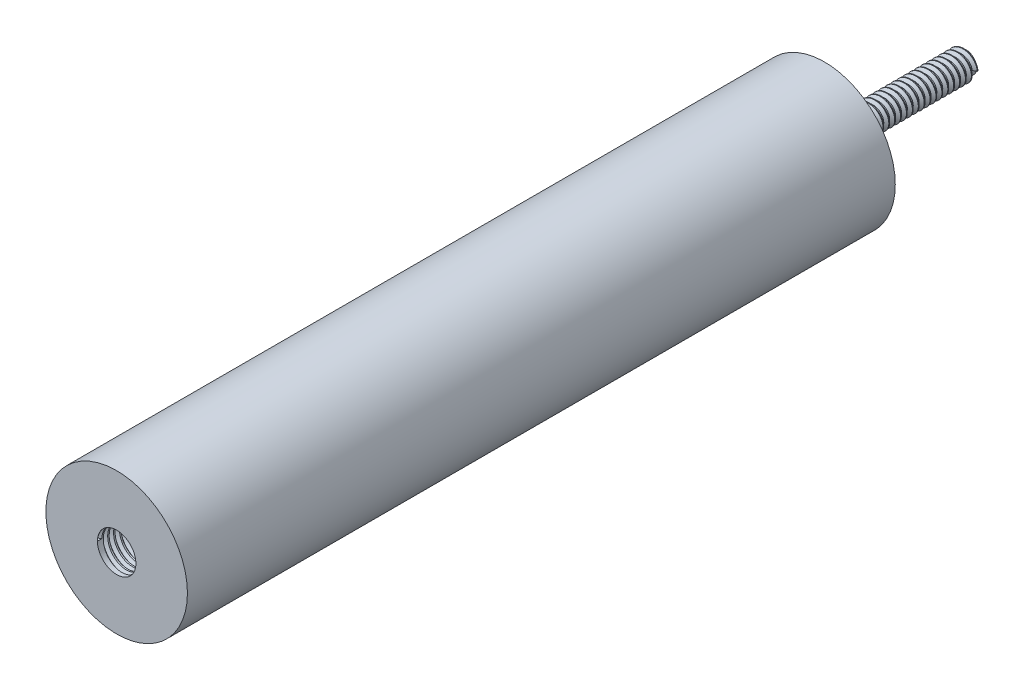
SolidWorks part; units mm, degrees
material "Cast Carbon Steel"
ref_plane "Front Plane" through (0, 0, 0) normal (0, 0, 1) x (1, 0, 0)
ref_plane "Top Plane" through (0, 0, 0) normal (0, 1, 0) x (1, 0, 0)
ref_plane "Right Plane" through (0, 0, 0) normal (1, 0, 0) x (0, 0, -1)
sketch "Sketch1" plane through (0, 0, 0) normal (0, 0, 1) x (1, 0, 0)
  line L1 (0, 0) -> (25.4, 0)
  line L2 (0, 0) -> (0, 32.766)
  line L3 (0, 32.766) -> (25.4, 32.766)
  line L4 (25.4, 0) -> (25.4, 32.766)
  dimension "D1" = 25.4
  dimension "D2" = 32.766
extrude "Boss-Extrude1" add sketch "Sketch1" against normal blind 127
sketch "Sketch2" plane through (0, 0, 0) normal (0, 0, 1) x (1, 0, 0)
  line L0 (25.4, 32.766) -> (0, 32.766) construction
  line L1 (25.4, 0) -> (25.4, 32.766) construction
  line L3 (0, 32.766) -> (25.4, 32.766)
  line L4 (0, 32.766) -> (0, 0)
  line L5 (0, 0) -> (25.4, 0)
  line L6 (25.4, 32.766) -> (25.4, 0)
  circle A0 centre (12.7, 16.383) radius 2.4574
  dimension "D1" = 4.9149
  dimension "D2" = 16.383
  dimension "D3" = 12.7
extrude "Cut-Extrude2" cut sketch "Sketch2" against normal blind 25.4
sketch "Sketch5" plane through (0, 0, -25.4) normal (0, 0, 1) x (1, 0, 0)
  line L0 (25.4, 32.766) -> (0, 32.766) construction
  line L1 (25.4, 0) -> (25.4, 32.766) construction
  line L3 (0, 32.766) -> (25.4, 32.766)
  line L4 (0, 32.766) -> (0, 0)
  line L5 (0, 0) -> (25.4, 0)
  line L6 (25.4, 32.766) -> (25.4, 0)
  circle A0 centre (12.7, 16.383) radius 12.7
  line M1 (0, 32.766) -> (0, 0)
  line M2 (0, 0) -> (25.4, 0)
  line M3 (25.4, 0) -> (25.4, 32.766)
  line M4 (25.4, 32.766) -> (0, 32.766)
  dimension "D1" = 16.383
  dimension "D3" = 25.4
  dimension "D2" = 12.7
extrude "Cut-Extrude3" cut sketch "Sketch5" against normal up to surface (101.6 mm away) contours A0 L6 M4 M1 | A0 L4 M2 M3 region at (12.7, 32.4637, -25.4) region at (12.7, 3.3807, -25.4) up to face at (12.7, 16.383, -127)
sketch "Sketch7" plane through (0, 0, -127) normal (0, 0, -1) x (-1, 0, 0)
  circle A0 centre (-12.7, 16.383) radius 1.8986
  dimension "D1" = 3.7973
extrude "Boss-Extrude2" add sketch "Sketch7" along normal blind 25.4
thread "Thread3" pitch 1.0583 method extrude profile "Thread Profile3" start angle 0, offset 0, length 0, pitch 1.0583, diameter 3.7973
ref_plane "Plane4" through (14.5986, 16.383, -152.4) normal (0, -1, 0) x (1, 0, 0)
sketch "Thread Profile3" plane through (14.5986, 16.383, -152.4) normal (0, -1, 0) x (1, 0, 0)
  line L0 (0, 0) -> (0, 1.0583) construction
  line L1 (0, 0) -> (0.5728, 0.3307)
  line L2 (0.5728, 0.3307) -> (0.5728, 0.463)
  line L3 (0.5728, 0.463) -> (0, 0.7937)
  line L4 (0.5728, 0.3969) -> (0, 0.3969) construction
  line L11 (0, 0) -> (0, 0.7937)
  point P2 (0, 0)
  dimension "Pitch" = 1.0583
  dimension "Profile_Angle" = 60
  dimension "Profile_Land" = 0.1323
  dimension "Profile_Height" = 0.5728
sketch "Sketch10" plane through (0, 0, -25.4) normal (0, 0, 1) x (1, 0, 0)
  circle A0 centre (12.7, 16.383) radius 12.7
  dimension "D1" = 25.4
extrude "Boss-Extrude3" add sketch "Sketch10" along normal blind 25.4
sketch "Sketch11" plane through (0, 0, 0) normal (0, 0, 1) x (1, 0, 0)
  circle A0 centre (12.7, 16.383) radius 3.4544
  dimension "D1" = 6.9088
extrude "Cut-Extrude4" cut sketch "Sketch11" against normal blind 12.7
thread "Thread4" pitch 1.0583 method cut profile "Thread Profile4" start angle 0, offset 0, length 0, pitch 1.0583, diameter 6.9088
ref_plane "Plane5" through (9.2456, 16.383, 0) normal (0, -1, 0) x (-1, 0, 0)
sketch "Thread Profile4" plane through (9.2456, 16.383, 0) normal (0, -1, 0) x (-1, 0, 0)
  line L0 (0, 0) -> (0, 1.0583) construction
  line L1 (0, 0) -> (0.5728, 0.3307)
  line L2 (0.5728, 0.3307) -> (0.5728, 0.463)
  line L3 (0.5728, 0.463) -> (0, 0.7937)
  line L4 (0.5728, 0.3969) -> (0, 0.3969) construction
  line L11 (0, 0) -> (0, 0.7937)
  point P2 (0, 0)
  dimension "Pitch" = 1.0583
  dimension "Profile_Angle" = 60
  dimension "Profile_Land" = 0.1323
  dimension "Profile_Height" = 0.5728
